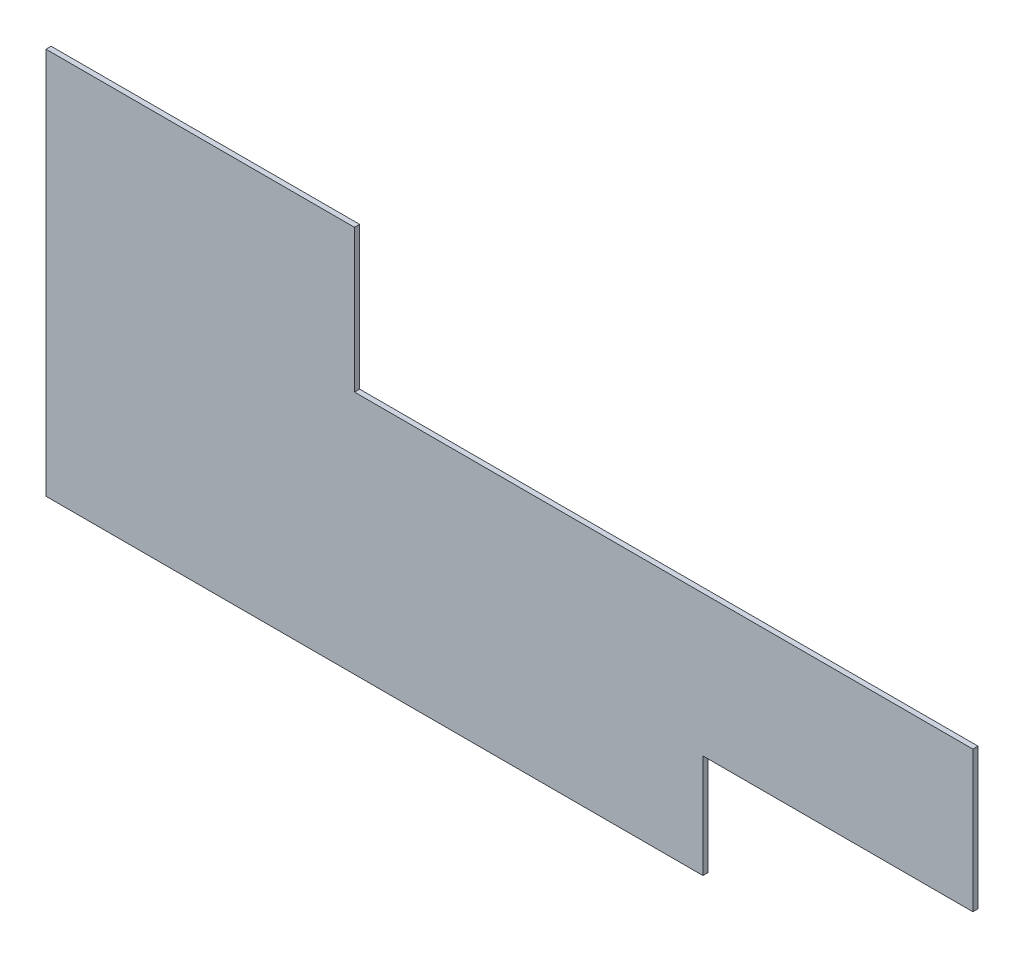
SolidWorks part; units mm, degrees
ref_plane "Ön Düzlem" through (0, 0, 0) normal (0, 0, 1) x (1, 0, 0)
ref_plane "Üst Düzlem" through (0, 0, 0) normal (0, 1, 0) x (1, 0, 0)
ref_plane "Sağ Düzlem" through (0, 0, 0) normal (1, 0, 0) x (0, 0, -1)
sketch "Çizim1" plane through (0, 0, 0) normal (0, 0, 1) x (1, 0, 0)
  line L0 (0, 0) -> (1200, 0)
  line L1 (1200, 0) -> (1200, -555)
  line L2 (1200, -555) -> (3605, -555)
  line L3 (3605, -555) -> (3605, -1103)
  line L4 (3605, -1103) -> (6010, -1103)
  line L5 (6010, -1103) -> (6010, -1506)
  line L6 (6010, -1506) -> (0, -1506)
  line L7 (0, -1506) -> (0, 0)
  dimension "D1" = 1200
  dimension "D2" = 555
  dimension "D3" = 548
  dimension "D4" = 2405
  dimension "D5" = 3605
  dimension "D6" = 1103
  dimension "D7" = 403
  dimension "D8" = 2405
  dimension "D9" = 6010
  dimension "D10" = 1506
base flange "Taban-Flanş1" sketch "Çizim1" thickness 20 reverse thickness direction no parameters "D1"=12
sketch "Çizim2" plane through (0, 0, 0) normal (0, 0, 1) x (1, 0, 0)
  line L0 (0, -1506) -> (6010, -1506) construction
  line L1 (6010, -1103) -> (2555, -1103)
  line L2 (6010, -1103) -> (6010, -1506)
  line L3 (6010, -1506) -> (2555, -1506)
  line L4 (2555, -1103) -> (2555, -1506)
  line L5 (3605, -1103) -> (3605, -555) construction
  line L6 (3605, -555) -> (1200, -555) construction
  dimension "D1" = 1050
  dimension "D2" = 403
  dimension "D3" = 548
extrude "Kes-Ekstrüzyon1" cut sketch "Çizim2" against normal through all both and the other way through all
sketch "Çizim3" plane through (0, 0, 0) normal (0, 0, 1) x (1, 0, 0)
  line L0 (1200, -555) -> (1200, 0) construction
  line L1 (3605, -555) -> (1265, -555)
  line L2 (3605, -555) -> (3605, -1095)
  line L3 (3605, -1095) -> (1265, -1095)
  line L4 (1265, -555) -> (1265, -1095)
  line L5 (1265, -555) -> (1200, -555)
  line L6 (1265, -555) -> (1265, -1095)
  line L7 (1265, -1095) -> (1200, -1095)
  line L8 (1200, -555) -> (1200, -1095)
  line L10 (2555, -1103) -> (3605, -1103)
  line L11 (2555, -1103) -> (2555, -1095)
  line L12 (2555, -1095) -> (3605, -1095)
  line L13 (3605, -1103) -> (3605, -1095)
  dimension "D1" = 540
  dimension "D2" = 2340
  dimension "D3" = 65
  dimension "D4" = 540
  dimension "D5" = 2405
  dimension "D6" = 8
  dimension "D7" = 1050
sketch "Büküm-Çizgileri1" [suppressed] plane through (0, 0, 0) normal (0, 1, 0) x (1, 0, 0)
sketch "Sınırlandırma-Kutusu1" [suppressed] plane through (0, 0, 0) normal (0, 1, 0) x (1, 0, 0)
sheet metal parameters "Sac-Levha1" thickness 20 parameters "D1"=12
flat pattern "Düz-Çoğaltma1" [suppressed]
sketch "Büküm-Çizgileri2" plane through (0, 0, 0) normal (0, 1, 0) x (1, 0, 0)
sketch3d "Sınırlandırma-Kutusu2" [suppressed]
  line L0 (0, -1506, 0) -> (-6010, -1506, 0) construction
  line L1 (0, 0, 0) -> (-6010, 0, 0) construction
  line L2 (0, -1506, 0) -> (0, 0, 0) construction
  line L3 (-6010, -1506, 0) -> (-6010, 0, 0) construction
sheet metal parameters "Sac-Levha2" thickness 20 parameters "D1"=12
flat pattern "Düz-Çoğaltma1"
sketch "Büküm-Çizgileri2" plane through (0, 0, 0) normal (0, 1, 0) x (1, 0, 0)
sketch3d "Sınırlandırma-Kutusu2" [suppressed]
  line L0 (0, -1506, 0) -> (3605, -1506, 0) construction
  line L1 (0, 0, 0) -> (3605, 0, 0) construction
  line L2 (0, -1506, 0) -> (0, 0, 0) construction
  line L3 (3605, -1506, 0) -> (3605, 0, 0) construction
